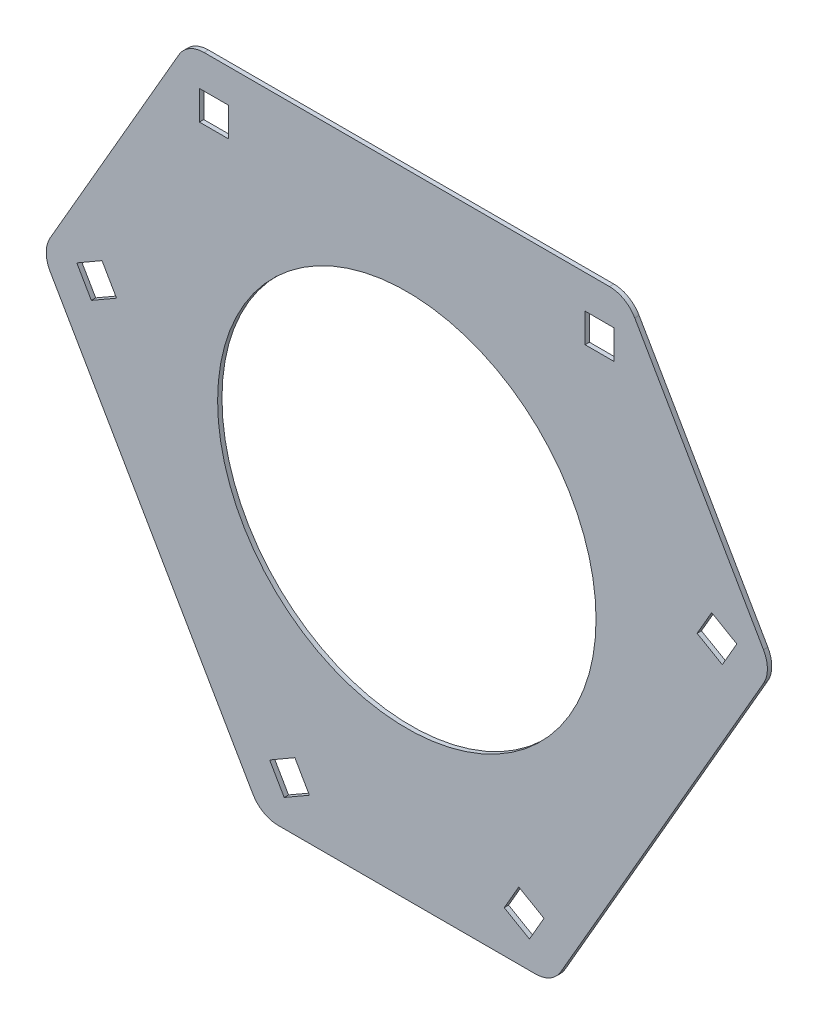
SolidWorks part; units mm, degrees
ref_plane "前视基准面" through (0, 0, 0) normal (0, 0, 1) x (1, 0, 0)
ref_plane "上视基准面" through (0, 0, 0) normal (0, 1, 0) x (1, 0, 0)
ref_plane "右视基准面" through (0, 0, 0) normal (1, 0, 0) x (0, 0, -1)
other "Configuration Table"
sketch "草图1" plane through (0, 0, 0) normal (0, 0, 1) x (1, 0, 0)
  line L0 (150.8286, 202.551) -> (-150.8286, 202.551)
  line L1 (-150.8286, 202.551) -> (-250.8286, 29.3459)
  line L2 (-250.8286, 29.3459) -> (-100, -231.8969)
  line L3 (-100, -231.8969) -> (100, -231.8969)
  line L4 (100, -231.8969) -> (250.8286, 29.3459)
  line L6 (-200.8286, 115.9485) -> (175.4143, -101.2755) construction
  line L7 (0, 202.551) -> (0, -231.8969) construction
  line L8 (-175.4143, -101.2755) -> (200.8262, 115.9471)
  line L9 (150.8286, 202.551) -> (250.8286, 29.3459)
  circle A0 centre (0, 0) radius 130
  point P7 (0, 0)
  point P70 (-122.2962, -44.0868)
  dimension "D3" = 260
  dimension "D1" = 120
  dimension "D2" = 120
  dimension "D6" = 200
extrude "凸台-拉伸1" add sketch "草图1" along normal blind 3
sketch "草图8" plane through (0, 0, 3) normal (0, 0, 1) x (1, 0, 0)
  line L0 (-142.5, 179.551) -> (-142.5, 159.551)
  line L1 (-142.5, 179.551) -> (-122.5, 179.551)
  line L2 (-142.5, 159.551) -> (-122.5, 159.551)
  line L3 (-122.5, 179.551) -> (-122.5, 159.551)
  line L4 (-175.4143, -101.2755) -> (0, 0)
  line L5 (-209.4252, 43.6331) -> (-226.7457, 33.6331)
  line L6 (-209.4252, 43.6331) -> (-199.4252, 26.3126)
  line L7 (-226.7457, 33.6331) -> (-216.7457, 16.3126)
  line L8 (-199.4252, 26.3126) -> (-216.7457, 16.3126)
  line L9 (-84.2457, -213.1841) -> (-66.9252, -203.1841)
  line L10 (-84.2457, -213.1841) -> (-94.2457, -195.8636)
  line L11 (-66.9252, -203.1841) -> (-76.9252, -185.8636)
  line L12 (-94.2457, -195.8636) -> (-76.9252, -185.8636)
  line L13 (66.9252, -203.1841) -> (84.2457, -213.1841)
  line L14 (66.9252, -203.1841) -> (76.9252, -185.8636)
  line L15 (84.2457, -213.1841) -> (94.2457, -195.8636)
  line L16 (76.9252, -185.8636) -> (94.2457, -195.8636)
  line L17 (209.4252, 43.6331) -> (199.4252, 26.3126)
  line L18 (209.4252, 43.6331) -> (226.7457, 33.6331)
  line L19 (199.4252, 26.3126) -> (216.7457, 16.3126)
  line L20 (226.7457, 33.6331) -> (216.7457, 16.3126)
  line L21 (142.5, 179.551) -> (142.5, 159.551)
  line L22 (142.5, 179.551) -> (122.5, 179.551)
  line L23 (142.5, 159.551) -> (122.5, 159.551)
  line L24 (122.5, 179.551) -> (122.5, 159.551)
  line L25 (0, 0) -> (175.4143, -101.2755)
  line L26 (0, 202.551) -> (0, 0)
  line L28 (150.8286, 202.551) -> (-150.8286, 202.551) construction
  line L29 (100, -231.8969) -> (250.8286, 29.3459) construction
  line L31 (-250.8286, 29.3459) -> (-100, -231.8969) construction
  dimension "D1" = 20
  dimension "D2" = 20
  dimension "D3" = 20
  dimension "D4" = 20
  dimension "D5" = 20
  dimension "D6" = 20
  dimension "D7" = 20
  dimension "D8" = 20
  dimension "D9" = 20
  dimension "D10" = 20
  dimension "D11" = 23
  dimension "D12" = 245
  dimension "D13" = 245
  dimension "D14" = 23
  dimension "D15" = 245
  dimension "D16" = 23
  dimension "D17" = 122.5
  dimension "D18" = 122.5
  dimension "D19" = 122.5
  dimension "D21" = 20
  dimension "D22" = 20
extrude "切除-拉伸4" cut sketch "草图8" against normal through all contours L0 L1 L3 L2 | L5 L6 L8 L7 | L21 L22 L24 L23 | L17 L18 L20 L19 | L9 L10 L12 L11 | L13 L14 L16 L15
fillet "圆角2" radius 20 6 edges at (100, -231.8969, 1.5) (-100, -231.8969, 1.5) (150.8286, 202.551, 1.5) (250.8286, 29.3459, 1.5) (-250.8286, 29.3459, 1.5) (-150.8286, 202.551, 1.5)
